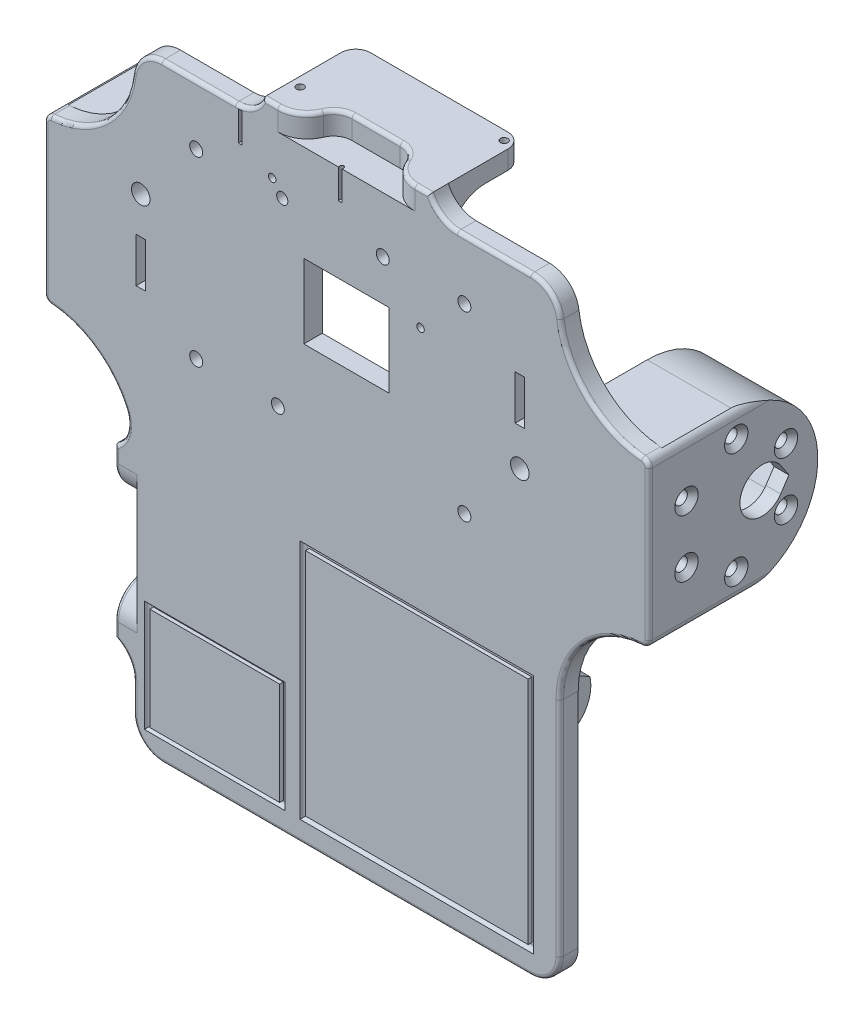
SolidWorks part; units mm, degrees
ref_plane "Front Plane" through (0, 0, 0) normal (0, 0, 1) x (1, 0, 0)
ref_plane "Top Plane" through (0, 0, 0) normal (0, 1, 0) x (1, 0, 0)
ref_plane "Right Plane" through (0, 0, 0) normal (1, 0, 0) x (0, 0, -1)
sketch "Sketch1" plane through (0, 0, 0) normal (0, 0, 1) x (1, 0, 0)
  line L0 (0, 0) -> (7, 5.25) construction
  line L1 (0, 0) -> (115, 0)
  line L2 (0, 0) -> (0, 100)
  line L3 (0, 100) -> (115, 100)
  line L4 (115, 0) -> (115, 100)
  line L5 (7, 94.75) -> (108, 94.75) construction
  line L6 (7, 94.75) -> (7, 5.25) construction
  line L7 (7, 5.25) -> (108, 5.25) construction
  line L8 (108, 94.75) -> (108, 5.25) construction
  line L9 (7, 94.75) -> (0, 100) construction
  line L10 (115, 100) -> (108, 94.75) construction
  line L11 (7, 94.75) -> (67.3, 84) construction
  line L12 (67.3, 84) -> (65.55, 84) construction
  line L13 (17, 36.75) -> (17, 35) construction
  line L14 (17, 35) -> (89.3, 35) construction
  line L15 (89.3, 36.75) -> (89.3, 35) construction
  line L17 (108, 5.25) -> (89.3, 35) construction
  line L18 (17, 35) -> (15.6741, 33.8579) construction
  circle A4 centre (67.3, 84) radius 1.75
  circle A6 centre (89.3, 35) radius 1.75
  circle A7 centre (17, 35) radius 1.75
  point P12 (10.5, 8.2648)
  point P19 (38.2404, 64.75)
  dimension "D5" = 10
  dimension "D7" = 3.5
  dimension "D1" = 100
  dimension "D2" = 115
  dimension "D3" = 89.5
  dimension "D4" = 101
  dimension "D6" = 50.3
  dimension "D8" = 72.3
  dimension "D9" = 49
  dimension "D10" = 35
extrude "Boss-Extrude1" add sketch "Sketch1" along normal blind 5
sketch "Sketch2" plane through (0, 0, 5) normal (0, 0, 1) x (1, 0, 0)
  line L0 (115, 0) -> (115, 100) construction
  line L1 (0, 0) -> (115, 0)
  line L2 (0, 0) -> (0, -64)
  line L3 (0, -64) -> (115, -64)
  line L4 (115, 0) -> (115, -64)
  dimension "D1" = 64
extrude "Boss-Extrude2" add sketch "Sketch2" against normal up to surface (5 mm away) up to face at (91.05, 35, 0)
sketch "Sketch3" plane through (0, 0, 5) normal (0, 0, 1) x (1, 0, 0)
  line L1 (46.5, 5) -> (106.5, 5)
  line L2 (46.5, 5) -> (46.5, -57)
  line L3 (46.5, -57) -> (106.5, -57)
  line L4 (106.5, 5) -> (106.5, -57)
  line L5 (46.5, 5) -> (106.5, -57) construction
  line L6 (3, -28.5) -> (41, -58.5) construction
  line L7 (108, -58.5) -> (45, -58.5)
  line L8 (108, -58.5) -> (108, 6.5)
  line L9 (108, 6.5) -> (45, 6.5)
  line L10 (45, -58.5) -> (45, 6.5)
  line L11 (108, -58.5) -> (45, 6.5) construction
  line L12 (108, 6.5) -> (45, -58.5) construction
  line L13 (3, -28.5) -> (41, -28.5)
  line L14 (3, -28.5) -> (3, -58.5)
  line L15 (3, -58.5) -> (41, -58.5)
  line L16 (41, -28.5) -> (41, -58.5)
  line L17 (115, -64) -> (115, 100) construction
  line L18 (39.5, -57.3158) -> (4.5, -57.3158)
  line L19 (39.5, -57.3158) -> (39.5, -29.6842)
  line L20 (39.5, -29.6842) -> (4.5, -29.6842)
  line L21 (4.5, -57.3158) -> (4.5, -29.6842)
  line L22 (39.5, -57.3158) -> (4.5, -29.6842) construction
  line L23 (39.5, -29.6842) -> (4.5, -57.3158) construction
  line L24 (0, 100) -> (0, -64) construction
  circle A0 centre (17, 35) radius 1.75 construction
  point P8 (76.5, -26)
  point P17 (22, -43.5)
  point P18 (22, -43.5)
  dimension "D1" = 62
  dimension "D2" = 60
  dimension "D3" = 7
  dimension "D4" = 30
  dimension "D5" = 1.5
  dimension "D6" = 1.5
  dimension "D7" = 1.5
  dimension "D8" = 38
  dimension "D9" = 3
  dimension "D10" = 30
sketch "Sketch4" plane through (0, 100, 0) normal (0, 1, 0) x (1, 0, 0)
  line L0 (115, -5) -> (0, -5) construction
  line L2 (80, -5) -> (80, 20)
  line L3 (80, 20) -> (35, 20)
  line L4 (35, -5) -> (35, 20)
  line L5 (57.5, -5) -> (35, 20) construction
  line L6 (80, 20) -> (57.5, -5) construction
  line L7 (115, 0) -> (0, 0) construction
  line L8 (35, -5) -> (80, -5)
  point P0 (57.5, -5)
  dimension "D1" = 20
  dimension "D2" = 45
extrude "Boss-Extrude3" add sketch "Sketch4" along normal blind 5
sketch "Sketch5" plane through (0, 105, 0) normal (0, 1, 0) x (1, 0, 0)
  line L1 (0, 0) -> (115, 0) construction
  line L2 (35, 20) -> (35, -5) construction
  line L3 (80, -5) -> (80, 20) construction
  line L5 (80, 20) -> (35, 20) construction
  line L6 (35, 20) -> (46, -5) construction
  line L7 (46, 0) -> (69, 0) construction
  line L8 (46, 0) -> (46, -5) construction
  line L9 (46, -5) -> (69, -5) construction
  line L10 (69, 0) -> (69, -5) construction
  line L11 (69, -5) -> (80, 20) construction
  line L12 (35, -5) -> (80, -5) construction
  circle A0 centre (37.5, 2.5) radius 1
  circle A1 centre (77.5, 17.5) radius 1
  dimension "D5" = 2
  dimension "D1" = 2.5
  dimension "D2" = 2.5
  dimension "D3" = 2.5
  dimension "D4" = 2.5
  dimension "D6" = 5
  dimension "D7" = 23
extrude "Cut-Extrude2" cut sketch "Sketch5" against normal through all
fillet "Fillet1" radius 10 1 edges at (57.5, 100, 0)
sketch "Sketch6" plane through (0, 100, 0) normal (0, -1, 0) x (1, 0, 0)
  circle A0 centre (37.5, -2.5) radius 2.25
  dimension "D1" = 4.5
extrude "Cut-Extrude3" cut sketch "Sketch6" along normal through all
sketch "Sketch7" plane through (0, 105, 0) normal (0, 1, 0) x (1, 0, 0)
  line L1 (46, 3) -> (69, 3)
  line L2 (46, 3) -> (46, -5)
  line L3 (46, -5) -> (69, -5)
  line L4 (69, 3) -> (69, -5)
  dimension "D1" = 8
extrude "Cut-Extrude4" cut sketch "Sketch7" against normal blind 6
sketch "Sketch8" plane through (0, 0, 0) normal (0, 0, -1) x (-1, 0, 0)
  line L0 (-35, 90) -> (-35, 100) construction
  line L1 (-80, 90) -> (-35, 90) construction
  line L2 (-80, 90) -> (-80, 70) construction
  line L3 (-80, 70) -> (-35, 70) construction
  line L4 (-35, 90) -> (-35, 70) construction
  line L5 (-80, 70) -> (-69, 53) construction
  line L6 (-69, 73) -> (-46, 73)
  line L7 (-69, 73) -> (-69, 53)
  line L8 (-69, 53) -> (-46, 53)
  line L9 (-46, 73) -> (-46, 53)
  line L10 (-46, 53) -> (-35, 70) construction
  circle A0 centre (-37.5, 87.5) radius 1
  circle A1 centre (-77.5, 72.5) radius 1
  dimension "D2" = 2
  dimension "D3" = 2.5
  dimension "D5" = 2.5
  dimension "D1" = 20
  dimension "D4" = 2.5
  dimension "D6" = 2.5
  dimension "D7" = 23
  dimension "D8" = 20
  dimension "D9" = 3
extrude "Cut-Extrude5" cut sketch "Sketch8" against normal through all
ref_plane "Plane1" through (57.5, 0, 0) normal (-1, 0, 0) x (0, 0, 1)
sketch "Sketch9" plane through (115, 0, 0) normal (1, 0, 0) x (0, 0, -1)
  line L0 (0, 0) -> (0, 28) construction
  line L2 (0, 50) -> (18.6, 50) construction
  line L4 (18.6, 72) -> (0, 72)
  line L6 (18.6, 28) -> (0, 28)
  line L8 (-5, -64) -> (-5, 100) construction
  line L9 (0, 72) -> (-5, 72)
  line L11 (0, 28) -> (-5, 28)
  line L13 (-5, 72) -> (-5, 28)
  circle A0 centre (18.6, 50) radius 18.5
  arc A1 (18.6, 28) -> (18.6, 72) centre (18.6, 50) ccw
  dimension "D2" = 37
  dimension "D3" = 44
  dimension "D1" = 50
  dimension "D4" = 18.6
extrude "Boss-Extrude4" add sketch "Sketch9" along normal blind 20 separate body
sketch "Sketch10" plane through (135, 0, 0) normal (1, 0, 0) x (0, 0, -1)
  line L0 (18.6, 50) -> (34.1, 50) construction
  line L1 (32.0234, 57.75) -> (18.6, 50) construction
  line L2 (-5, 28) -> (18.6, 28) construction
  line L4 (18.6, 72) -> (-5, 72) construction
  line L5 (-5, 28) -> (18.6, 28)
  line L6 (-5, 72) -> (-5, 28)
  line L7 (18.6, 72) -> (-5, 72)
  circle A2 centre (18.6, 50) radius 18.5 construction
  circle A3 centre (18.6, 50) radius 18.5 construction
  circle A4 centre (25.6, 50) radius 6
  circle A5 centre (18.6, 50) radius 15.5 construction
  arc A6 (18.6, 28) -> (18.6, 72) centre (18.6, 50) ccw
  point P11 (32.0234, 57.75)
  point P17 (32.0234, 42.25)
  point P18 (18.6, 34.5)
  point P19 (5.1766, 42.25)
  point P20 (5.1766, 57.75)
  point P21 (18.6, 65.5)
  point P22 (18.6, 50)
  dimension "D1" = 12
  dimension "D3" = 31
  dimension "D2" = 7
  dimension "D4" = 30
  dimension "D5" = 6
extrude "Boss-Extrude5" add sketch "Sketch10" along normal blind 4
hole_wizard "CSK for M3 Flat Head Machine Screw1" positions "Sketch11" profile "Sketch12" countersink size "M3" standard "ANSI Metric" end condition through all
sketch "Sketch11" plane through (139, 0, 0) normal (1, 0, 0) x (0, 0, -1)
  point P0 (32.0234, 57.75)
  point P3 (18.6, 65.5)
  point P6 (5.1766, 57.75)
  point P9 (5.1766, 42.25)
  point P12 (18.6, 34.5)
  point P15 (32.0234, 42.25)
sketch "Sketch12" plane through (139, 57.75, -32.0234) normal (0, 1, 0) x (0, 0, -1)
  line L0 (0, 0) -> (0, 139)
  line L1 (0, 139) -> (1.7, 139)
  line L2 (1.7, 139) -> (1.7, 1.45)
  line L3 (1.7, 1.45) -> (3.15, 0)
  line L5 (3.15, 0) -> (0, 0)
  line L6 (-1.7, 1.45) -> (-3.15, 0) construction
  line L11 (0, -6.35) -> (0, 107.95) construction
  dimension "Thru Hole Dia." = 3.4
  dimension "Thru Hole Depth" = 139
  dimension "Near C'Sink Dia." = 6.3
  dimension "Near C'Sink Angle" = 90
mirror "Mirror10" about plane through (57.5, 0, 0) normal (-1, 0, 0) of "CSK for M3 Flat Head Machine Screw1", "Boss-Extrude5", "Boss-Extrude4"
sketch "Sketch15" plane through (0, 0, 0) normal (0, 0, -1) x (-1, 0, 0)
  line L0 (-139, 72) -> (-115, 72) construction
  line L1 (-115, -64) -> (-115, 100) construction
  line L2 (-139, 28) -> (-115, 28) construction
  line L3 (0, 28) -> (0, -64) construction
  line L4 (24, 28) -> (0, 28) construction
  line L5 (0, 100) -> (0, 72) construction
  line L6 (24, 72) -> (0, 72) construction
  line L7 (24, 72) -> (0, 72)
  line L8 (0, 72) -> (0, 96)
  line L9 (24, 28) -> (0, 28)
  line L10 (0, 28) -> (0, 4)
  line L11 (-115, 4) -> (-115, 28)
  line L12 (-115, 28) -> (-115, 72) construction
  line L13 (-115, 28) -> (-139, 28)
  line L14 (-115, 96) -> (-115, 72)
  line L15 (-115, 72) -> (-139, 72)
  arc A0 (-139, 72) -> (-115, 96) centre (-139, 96) ccw
  arc A1 (-115, 4) -> (-139, 28) centre (-139, 4) ccw
  arc A2 (0, 96) -> (24, 72) centre (24, 96) ccw
  arc A3 (24, 28) -> (0, 4) centre (24, 4) ccw
extrude "Boss-Extrude6" add sketch "Sketch15" against normal up to surface (5 mm away) up to face at (36.5, 87.5, 5)
ref_plane "Plane2" through (50.4, 0, 0) normal (-1, 0, 0) x (0, 0, 1)
sketch "Sketch16" plane through (50.4, 0, 0) normal (-1, 0, 0) x (0, 0, 1)
  line L0 (0, -9.5117) -> (-32.8318, -28.4672)
  line L1 (0, 4) -> (0, -64) construction
  line L2 (0, -9.5117) -> (0, -24.5117)
  line L3 (0, -24.5117) -> (-28.1738, -40.7779)
  line L4 (0, -17.0117) -> (-34.35, -36.8437) construction
  line L5 (-32.8318, -28.4672) -> (-43.5456, -34.6528)
  line L6 (-28.1738, -40.7779) -> (-37.0504, -45.9028)
  circle A0 centre (-34.35, -36.8437) radius 3.5
  arc A2 (-43.5456, -34.6528) -> (-37.0504, -45.9028) centre (-34.35, -36.8437) ccw
  dimension "D4" = 7
  dimension "D1" = 15
  dimension "D2" = 120
  dimension "D3" = 34.35
extrude "Boss-Extrude7" add sketch "Sketch16" along normal blind 10
mirror "Mirror11" about plane through (57.5, 0, 0) normal (-1, 0, 0) of "Boss-Extrude7"
fillet "Fillet3" radius 20 2 edges at (40.4, -17.0117, 0) (74.6, -17.0117, 0)
fillet "Fillet4" radius 5 4 edges at (35.4, -24.5117, 0) (79.6, -24.5117, 0) (35.4, -9.5117, 0) (79.6, -9.5117, 0)
sketch "Sketch19" plane through (0, 0, 0) normal (-1, 0, 0) x (0, 0, 1)
  line L0 (5, 4) -> (-20, 4)
  line L1 (-20, 4) -> (-20, -41)
  line L2 (5, -41) -> (-20, -41)
  line L3 (5.2881, -18.5) -> (-20, -41) construction
  line L4 (-20, 4) -> (5.2881, -18.5) construction
  line L5 (5, -41) -> (5, 4)
  line L8 (5, 4) -> (0, 4) construction
  line L9 (5, 4) -> (5, -64) construction
  point P0 (5.2881, -18.5)
  dimension "D1" = 45
  dimension "D2" = 25
extrude "Boss-Extrude9" add sketch "Sketch19" along normal blind 5
sketch "Sketch20" plane through (-5, 0, 0) normal (-1, 0, 0) x (0, 0, 1)
  line L0 (-20, 4) -> (-20, -41) construction
  line L1 (5, 4) -> (-20, 4) construction
  line L2 (0, -41) -> (0, -64) construction
  line L3 (-20, -41) -> (5, -41) construction
  circle A0 centre (-17.5, 1.5) radius 1
  circle A1 centre (-2.5, -38.5) radius 1
  dimension "D2" = 2.5
  dimension "D3" = 2
  dimension "D1" = 2.5
  dimension "D4" = 2.5
  dimension "D5" = 2.5
extrude "Cut-Extrude6" cut sketch "Sketch20" against normal up to surface (5 mm away) up to face at (0, -18.5, -10)
fillet "Fillet5" radius 10 1 edges at (0, -18.5, 0)
sketch "Sketch21" plane through (-5, 0, 0) normal (-1, 0, 0) x (0, 0, 1)
  line L0 (5, -41) -> (5, 4) construction
  line L1 (5, -7) -> (-3, -7)
  line L2 (5, -7) -> (5, -30)
  line L3 (5, -30) -> (-3, -30)
  line L4 (-3, -7) -> (-3, -30)
  line L5 (5, 4) -> (-3, -7) construction
  line L6 (5, -41) -> (-3, -30) construction
  dimension "D1" = 8
  dimension "D2" = 23
extrude "Cut-Extrude7" cut sketch "Sketch21" against normal blind 6
sketch "Sketch22" plane through (0, 0, 0) normal (1, 0, 0) x (0, 0, -1)
  circle A0 centre (2.5, -38.5) radius 2.25
  dimension "D1" = 4.5
extrude "Cut-Extrude8" cut sketch "Sketch22" along normal blind 15
sketch "Sketch23" plane through (0, 0, 5) normal (0, 0, 1) x (1, 0, 0)
  line L1 (101, 63) -> (101, 75) construction
  line L2 (101, 63) -> (131, 63) construction
  line L3 (131, 63) -> (131, 75) construction
  line L4 (101, 75) -> (131, 75) construction
  line L6 (103, 63) -> (104.25, 53) construction
  line L7 (139, 72) -> (139, 28) construction
  line L8 (105.5, 63) -> (105.5, 75)
  line L9 (105.5, 63) -> (103, 63)
  line L10 (103, 63) -> (103, 75)
  line L11 (105.5, 75) -> (103, 75)
  line L12 (104.25, 53) -> (105.5, 63) construction
  circle A0 centre (104.25, 53) radius 2.5
  dimension "D6" = 5
  dimension "D1" = 30
  dimension "D2" = 12
  dimension "D3" = 36
  dimension "D4" = 2.5
  dimension "D5" = 4.5
  dimension "D7" = 10
  dimension "D8" = 3
extrude "Cut-Extrude10" cut sketch "Sketch23" against normal blind 22
extrude "Cut-Extrude11" cut sketch "Sketch3" against normal blind 1
fillet "Fillet6" radius 1 8 edges at (76.5, -58.5, 4) (108, -26, 4) (76.5, 6.5, 4) (45, -26, 4) (22, -58.5, 4) (41, -43.5, 4) (22, -28.5, 4) (3, -43.5, 4)
fillet "Fillet7" radius 5 4 edges at (69, 102, -3) (46, 102, -3) (-2, -7, -3) (-2, -30, -3)
sketch "Sketch24" plane through (115, 0, 0) normal (-1, 0, 0) x (0, 0, 1)
  line L0 (-18.6, 50) -> (-55.3503, 50) construction
  line L1 (-35.057, 41.5491) -> (-39.3966, 50)
  line L2 (-39.3966, 50) -> (-35.057, 58.4509)
  circle A0 centre (-18.6, 50) radius 18.5 construction
  arc A1 (-35.057, 58.4509) -> (-35.057, 41.5491) centre (-18.6, 50) ccw
  dimension "D1" = 9.5
extrude "Cut-Extrude12" cut sketch "Sketch24" against normal up to surface (20 mm away) up to face at (135, 57.75, -33.7234)
sketch "Sketch25" plane through (135, 0, 0) normal (-1, 0, 0) x (0, 0, 1)
  line L0 (-25.6, 50) -> (-44.9333, 50) construction
  line L1 (-30.5923, 46.6718) -> (-32.8111, 50)
  line L6 (-32.8111, 50) -> (-30.5923, 53.3282)
  circle A0 centre (-25.6, 50) radius 6 construction
  arc A3 (-30.5923, 53.3282) -> (-30.5923, 46.6718) centre (-25.6, 50) ccw
  dimension "D2" = 4
extrude "Cut-Extrude13" cut sketch "Sketch25" against normal through all
mirror "Mirror14" about plane through (57.5, 0, 0) normal (-1, 0, 0) of "Cut-Extrude13"
sketch "Sketch26" plane through (0, 0, 0) normal (1, 0, 0) x (0, 0, -1)
  line L0 (35.057, 58.4509) -> (39.3966, 50) construction
  line L1 (39.3966, 50) -> (35.057, 41.5491) construction
  line L2 (35.057, 58.4509) -> (39.3966, 50)
  line L3 (39.3966, 50) -> (35.057, 41.5491)
  arc A0 (35.057, 41.5491) -> (35.057, 58.4509) centre (18.6, 50) ccw
extrude "Cut-Extrude14" cut sketch "Sketch26" against normal up to surface (20 mm away) up to face at (-20, 50, -37.1)
sketch "Sketch27" plane through (74.6, 0, 0) normal (1, 0, 0) x (0, 0, -1)
  line L0 (34.35, -36.8437) -> (51.856, -36.8437) construction
  line L1 (36.6548, -39.4777) -> (39.6651, -36.8437)
  line L2 (39.6651, -36.8437) -> (36.6548, -34.2097)
  circle A0 centre (34.35, -36.8437) radius 3.5 construction
  arc A1 (36.6548, -39.4777) -> (36.6548, -34.2097) centre (34.35, -36.8437) ccw
  dimension "D1" = 4
extrude "Cut-Extrude15" cut sketch "Sketch27" against normal up to surface (34.2 mm away) up to face at (40.4, -34.7414, -30.7086)
fillet "Fillet8" radius 8 12 edges at (0, 100, 2.5) (115, 100, 2.5) (80, 100, 2.5) (35, 100, 2.5) (0, -41, 2.5) (0, 4, 2.5) (115, -64, 2.5) (0, -64, 2.5) (46, 102, 5) (69, 102, 5) (-2, -7, 5) (-2, -30, 5)
fillet "Fillet9" radius 4 4 edges at (80, 102.5, -20) (35, 102.5, -20) (-2.5, -41, -20) (-2.5, 4, -20)
sketch "Sketch28" plane through (0, 0, 5) normal (0, 0, 1) x (1, 0, 0)
  line L0 (-24, 72) -> (-24, 28) construction
  line L1 (139, 72) -> (139, 28) construction
  line L2 (-24, 72) -> (-24, 70.077)
  line L3 (139, 72) -> (139, 70.077)
  line L4 (139, 29.923) -> (139, 28)
  line L5 (-24, 29.923) -> (-24, 28)
  arc A0 (-2.1711, 13.9748) -> (-24, 28) centre (-24, 4) ccw construction
  arc A1 (-24, 72) -> (-0.1882, 93) centre (-24, 96) ccw construction
  arc A2 (139, 28) -> (115, 4) centre (139, 4) ccw construction
  arc A3 (115.1882, 93) -> (139, 72) centre (139, 96) ccw construction
  arc A4 (-22.1538, 27.9289) -> (-24, 28) centre (-24, 4) ccw
  arc A5 (-24, 72) -> (-22.1538, 72.0711) centre (-24, 96) ccw
  arc A6 (139, 28) -> (137.1538, 27.9289) centre (139, 4) ccw
  arc A7 (137.1538, 72.0711) -> (139, 72) centre (139, 96) ccw
  arc A8 (-22.1538, 72.0711) -> (-24, 70.077) centre (-22, 70.077) ccw
  arc A9 (-24, 29.923) -> (-22.1538, 27.9289) centre (-22, 29.923) ccw
  arc A10 (139, 70.077) -> (137.1538, 72.0711) centre (137, 70.077) ccw
  arc A11 (137.1538, 27.9289) -> (139, 29.923) centre (137, 29.923) ccw
  dimension "D1" = 2
extrude "Cut-Extrude16" cut sketch "Sketch28" against normal through all
fillet "Fillet10" radius 1 37 edges at (37, 105, 5) (78, 105, 5) (71.5624, 105, 3.6564) (66.7735, 105, -2.1603) (57.5, 105, -3) (48.2265, 105, -2.1603) (-1.3668, -43.9441, 5) (82.9441, 101.3668, 5) (97.3336, 100, 5) (112.5425, 98, 5) (122.4444, 78.6243, 5) (138.4676, 71.4358, 5) (139, 50, 5) (138.4676, 28.5642, 5) (121.3888, 20.3048, 5) (115, -26, 5) (112.6569, -61.6569, 5) (57.5, -64, 5) (2.3431, -61.6569, 5) (-5, -39, 5) (-5, -32.5624, 3.6564) (-5, -27.7735, -2.1603) (-5, -18.5, -3) (-5, -9.2265, -2.1603) (-5, 2, 5) (32.0559, 101.3668, 5) (17.6664, 100, 5) (2.4575, 98, 5) (-7.4444, 78.6243, 5) (-23.4676, 71.4358, 5) (-1.7509, 8.4671, 5) (-10.2593, 23.6772, 5) (-23.4676, 28.5642, 5) (43.4376, 105, 3.6564) (0, -52.2081, 5) (-5, -4.4376, 3.6564) (-24, 50, 5)
sketch "Sketch30" plane through (0, 0, 5) normal (0, 0, 1) x (1, 0, 0)
  line L0 (-24, 29.923) -> (-24, 70.077) construction
  line L1 (28.36, 99.1) -> (29.36, 99.1)
  line L2 (28.36, 99.1) -> (28.36, 91.1)
  line L3 (28.36, 91.1) -> (29.36, 91.1)
  line L4 (56.3, 99.1) -> (56.3, 91.1)
  line L5 (51, 105) -> (64, 105) construction
  line L6 (29.36, 99.1) -> (29.36, 91.1)
  line L7 (55.3, 99.1) -> (55.3, 91.1)
  line L8 (55.3, 99.1) -> (56.3, 99.1)
  line L9 (55.3, 91.1) -> (56.3, 91.1)
  dimension "D1" = 52.36
  dimension "D2" = 5.9
  dimension "D3" = 8
  dimension "D4" = 27.94
  dimension "D5" = 1
  dimension "D6" = 1
extrude "Cut-Extrude17" cut sketch "Sketch30" against normal blind 1
fillet "Fillet11" radius 0.5 4 edges at (56.3, 95.05, 4) (55.3, 95.05, 4) (29.36, 95.1, 4) (28.36, 95.1, 4)
sketch "Sketch31" plane through (0, 0, 5) normal (0, 0, 1) x (1, 0, 0)
  line L0 (17, 35) -> (67.3, 84) construction
  line L1 (-38.6633, 59.5) -> (93.6838, 59.5) construction
  line L2 (7.749, 100) -> (27.5838, 100) construction
  circle A0 centre (67.3, 84) radius 1.75 construction
  circle A1 centre (89.3, 35) radius 1.75 construction
  circle A2 centre (17, 35) radius 1.75 construction
  circle A3 centre (67.3, 84) radius 1.75
  circle A6 centre (89.3, 84) radius 1.75
  circle A7 centre (17, 84) radius 1.75
  circle A8 centre (39, 35) radius 1.75
  point P21 (39, 43.1279)
  dimension "D7" = 3.5
  dimension "D1" = 49
  dimension "D2" = 24.5
  dimension "D3" = 40.5
  dimension "D4" = 22
  dimension "D5" = 22
  dimension "D6" = 49
extrude "Cut-Extrude18" cut sketch "Sketch31" against normal through all
sketch "Sketch32" plane through (0, 0, 5) normal (0, 0, 1) x (1, 0, 0)
  line L0 (67.3, 84) -> (39, 35) construction
  line L1 (17, 35) -> (89.3, 84) construction
  line L2 (17, 84) -> (89.3, 35) construction
  line L7 (3.3, 56) -> (0.8, 56)
  line L8 (0.8, 56) -> (0.8, 44)
  line L9 (0.8, 44) -> (3.3, 44)
  line L10 (3.3, 44) -> (3.3, 56)
  circle A1 centre (2.05, 66) radius 2.5
  point P12 (53.15, 59.5)
extrude "Cut-Extrude19" cut sketch "Sketch32" against normal through all
sketch "Sketch33" plane through (0, 0, 5) normal (0, 0, 1) x (1, 0, 0)
  line L0 (7.749, 100) -> (27.5838, 100) construction
  line L1 (-23, 70.077) -> (-23, 29.923) construction
  circle A0 centre (40.1957, 84.105) radius 1.5
  point P2 (43.8175, 85.8653)
  dimension "D1" = 3
  dimension "D2" = 15.895
  dimension "D3" = 63.1957
extrude "Cut-Extrude20" cut sketch "Sketch33" against normal through all
